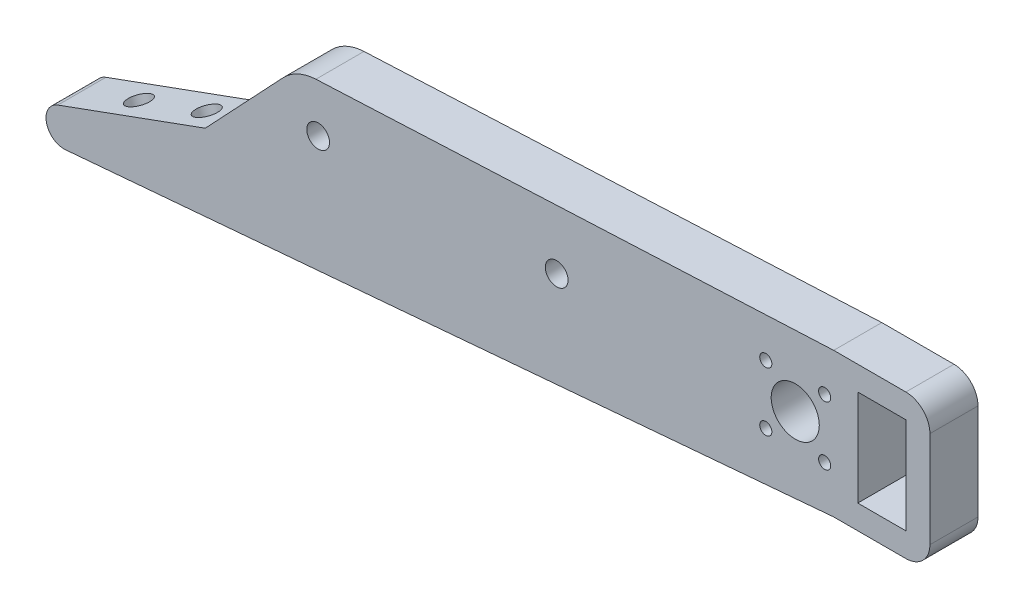
SolidWorks part; units mm, degrees
ref_plane "Front Plane" through (0, 0, 0) normal (0, 0, 1) x (1, 0, 0)
ref_plane "Top Plane" through (0, 0, 0) normal (0, 1, 0) x (1, 0, 0)
ref_plane "Right Plane" through (0, 0, 0) normal (1, 0, 0) x (0, 0, -1)
sketch "Sketch1" plane through (0, 0, 0) normal (0, 0, 1) x (1, 0, 0)
  line L0 (27.6069, 3.8891) -> (35.3851, -3.8891) construction
  line L1 (0, -3.4925) -> (0, 3.4925) construction
  line L2 (27.6069, -3.8891) -> (35.3851, 3.8891) construction
  line L3 (-1001.9207, 0) -> (48998.0793, 0) construction
  line L4 (-969.6313, -19.05) -> (49030.3687, -19.05) construction
  line L5 (36.576, 9.525) -> (49.276, 9.525)
  line L6 (39.751, 6.35) -> (46.101, 6.35)
  line L7 (39.751, 6.35) -> (39.751, -6.35)
  line L8 (39.751, -6.35) -> (46.101, -6.35)
  line L9 (46.101, 6.35) -> (46.101, -6.35)
  line L10 (39.751, 6.35) -> (46.101, -6.35) construction
  line L11 (39.751, -6.35) -> (46.101, 6.35) construction
  line L13 (36.576, -9.525) -> (49.276, -9.525)
  line L14 (36.576, 0) -> (36.576, -9.525) construction
  line L15 (49.276, 9.525) -> (49.276, -9.525)
  line L21 (36.576, 9.525) -> (36.576, 0) construction
  line L22 (36.576, 9.525) -> (36.576, -9.525) construction
  line L23 (-46.398, -6.562) -> (-80.7085, -19.05) construction
  line L24 (49.276, 9.525) -> (49.276, -9.525) construction
  line L25 (36.576, 9.525) -> (-31.7912, 6.3431)
  line L26 (-36.1188, 4.3534) -> (-46.398, -6.562)
  line L27 (-46.398, -6.562) -> (-65.8615, -13.6461)
  line L28 (-64.8428, -18.2563) -> (36.576, -9.525)
  circle A0 centre (31.496, 0) radius 3.175
  circle A1 centre (27.6069, 3.8891) radius 0.8
  circle A2 centre (35.3851, -3.8891) radius 0.8
  circle A4 centre (-31.496, 0) radius 1.5
  circle A5 centre (35.3851, 3.8891) radius 0.8
  circle A6 centre (27.6069, -3.8891) radius 0.8
  circle A7 centre (31.496, 0) radius 19.05 construction
  circle A8 centre (-31.496, 0) radius 19.05 construction
  arc A16 (-31.7912, 6.3431) -> (-36.1188, 4.3534) centre (-31.496, 0) ccw
  circle A17 centre (-29.9085, 22.225) radius 38.1 construction
  arc A18 (-65.8615, -13.6461) -> (-64.8428, -18.2563) centre (-65.0471, -15.8838) ccw
  arc A19 (-37.846, 0) -> (-25.146, 0) centre (-31.496, 0) ccw construction
  arc A21 (-25.146, 0) -> (-31.7912, 6.3431) centre (-31.496, 0) ccw construction
  arc A22 (-36.1188, 4.3534) -> (-37.846, 0) centre (-31.496, 0) ccw construction
  circle A23 centre (0, 0) radius 1.5
  point P6 (31.496, 0)
  point P17 (31.496, 0)
  point P33 (42.926, 0)
  point P51 (-29.9085, -15.875)
  point P52 (-68.0085, 22.225)
  dimension "D1" = 6.35
  dimension "D3" = 62.992
  dimension "D4" = 1.6
  dimension "D7" = 38.1
  dimension "D10" = 12.7
  dimension "D11" = 36.5125
  dimension "D16" = 1.5875
  dimension "D18" = 76.2
  dimension "D6" = 3
  dimension "D9" = 12.7
  dimension "D19" = 4.7625
  dimension "D2" = 11
  dimension "D5" = 45
  dimension "D8" = 20
  dimension "D12" = 6.35
  dimension "D13" = 12.7
  dimension "D15" = 11.43
  dimension "D17" = 3.175
  dimension "D20" = 1.5875
  dimension "D14" = 3.175
extrude "Boss-Extrude1" add sketch "Sketch1" along normal mid plane 6.35 contours L27 A18 L28 L13 L15 L5 L25 A16 L26 A4 A2 A1 A0 L6 L9 L8 L7 A5 A6 region at (-5.0143, -3.6936, 0)
fillet "Fillet1" radius 3.175 2 edges at (49.276, -9.525, 0) (49.276, 9.525, 0)
sketch "Sketch2" plane through (-3.3185, 9.1176, 0) normal (-0.342, 0.9397, 0) x (0.9397, 0.342, 0)
  line L0 (-58.5442, 0) -> (-49.0192, 0) construction
  line L1 (-49.0192, 0) -> (-45.8442, 0) construction
  line L2 (-45.8442, -3.175) -> (-45.8442, 3.175) construction
  circle A0 centre (-49.0192, 0) radius 1.5
  circle A1 centre (-58.5442, 0) radius 1.5
  dimension "D1" = 3
  dimension "D2" = 3.175
  dimension "D3" = 9.525
extrude "Cut-Extrude1" cut sketch "Sketch2" against normal blind 6
